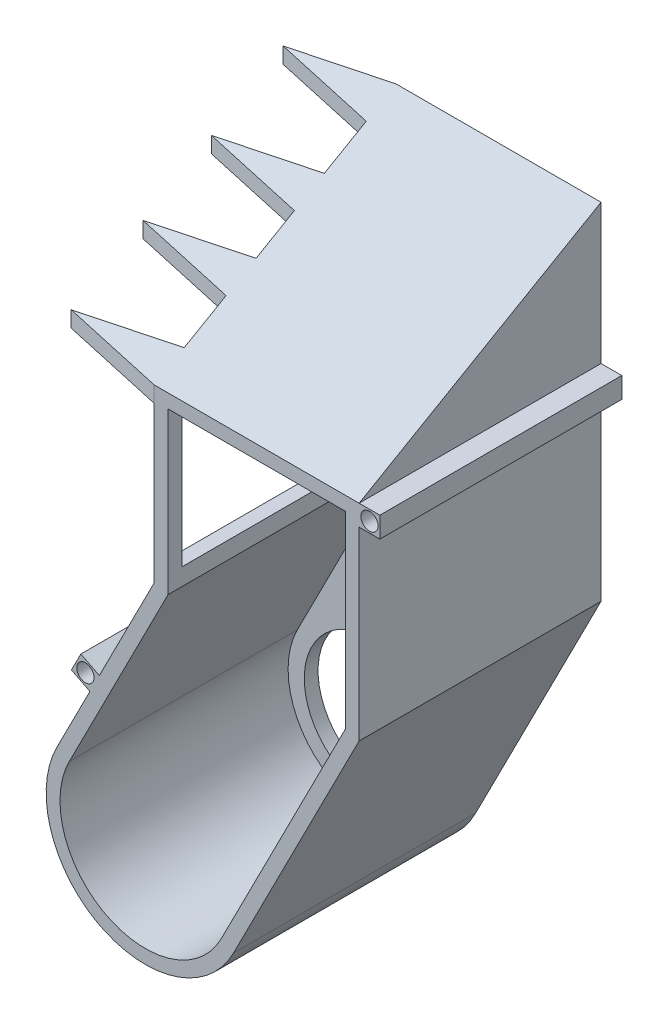
SolidWorks part; units mm, degrees
ref_plane "Front Plane" through (0, 0, 0) normal (0, 0, 1) x (1, 0, 0)
ref_plane "Top Plane" through (0, 0, 0) normal (0, 1, 0) x (1, 0, 0)
ref_plane "Right Plane" through (0, 0, 0) normal (1, 0, 0) x (0, 0, -1)
sketch "Sketch1" plane through (0, 0, 0) normal (0, 0, 1) x (1, 0, 0)
  line L0 (0, 0) -> (0, 26.0789) construction
  line L1 (-32.644, 168.714) -> (42.6346, 168.714)
  line L2 (42.6346, 168.714) -> (42.6346, 41.714)
  line L3 (42.6346, 41.714) -> (-3.4908, -48.8123)
  line L4 (-32.644, 168.714) -> (-32.644, 54.414)
  line L5 (-32.644, 54.414) -> (-68.3912, -15.7439)
  circle A0 centre (-23.0776, 43.8589) radius 3.175
  circle A1 centre (22.1344, 43.8589) radius 3.175
  circle A2 centre (-35.941, -32.2781) radius 25.4
  arc A3 (-68.3912, -15.7439) -> (-3.4908, -48.8123) centre (-35.941, -32.2781) ccw
  dimension "D1" = 50.8
  dimension "D2" = 45.212
  dimension "D3" = 6.35
  dimension "D4" = 6.35
  dimension "D11" = 101.6
  dimension "D5" = 77.216
  dimension "D6" = 95.758
  dimension "D7" = 35.941
  dimension "D8" = 17.78
  dimension "D9" = 153
  dimension "D10" = 127
  dimension "D12" = 78.74
  dimension "D13" = 114.3
  dimension "D14" = 19.05
extrude "Boss-Extrude1" add sketch "Sketch1" along normal blind 88.9
sketch "Sketch2" plane through (-32.644, 0, 0) normal (-1, 0, 0) x (0, 0, 1)
  line L0 (0, 168.714) -> (88.9, 117.3875)
  line L1 (88.9, 168.714) -> (88.9, 54.414) construction
  line L2 (88.9, 117.3875) -> (88.9, 168.714)
  line L3 (88.9, 168.714) -> (0, 168.714)
  dimension "D1" = 30
extrude "Cut-Extrude1" cut sketch "Sketch2" against normal through all
sketch "Sketch3" plane through (0, 0, 88.9) normal (0, 0, 1) x (1, 0, 0)
  line L10 (37.5546, 112.3075) -> (-27.564, 112.3075)
  line L11 (-27.564, 112.3075) -> (-27.564, 53.1944)
  line L12 (-27.564, 53.1944) -> (-63.8649, -18.0502)
  line L13 (-8.0171, -46.506) -> (37.5546, 42.9336)
  line L14 (37.5546, 42.9336) -> (37.5546, 112.3075)
  line L15 (37.5546, 112.3075) -> (-27.564, 112.3075)
  line L16 (-27.564, 112.3075) -> (-27.564, 53.1944)
  line L17 (-27.564, 53.1944) -> (-63.8649, -18.0502)
  line L18 (-8.0171, -46.506) -> (37.5546, 42.9336)
  line L19 (37.5546, 42.9336) -> (37.5546, 112.3075)
  arc A2 (-63.8649, -18.0502) -> (-8.0171, -46.506) centre (-35.941, -32.2781) ccw
  arc A3 (-63.8649, -18.0502) -> (-8.0171, -46.506) centre (-35.941, -32.2781) ccw
  dimension "D1" = 5.08
extrude "Cut-Extrude2" cut sketch "Sketch3" against normal blind 83.82
sketch "Sketch4" plane through (-32.644, 0, 0) normal (-1, 0, 0) x (0, 0, 1)
  line L8 (83.82, 59.494) -> (83.82, 114.4546)
  line L9 (83.82, 114.4546) -> (5.08, 159.9151)
  line L10 (5.08, 159.9151) -> (5.08, 59.494)
  line L11 (5.08, 59.494) -> (83.82, 59.494)
  line L12 (83.82, 59.494) -> (83.82, 114.4546)
  line L13 (83.82, 114.4546) -> (5.08, 159.9151)
  line L14 (5.08, 159.9151) -> (5.08, 59.494)
  line L15 (5.08, 59.494) -> (83.82, 59.494)
  dimension "D1" = 5.08
extrude "Cut-Extrude3" cut sketch "Sketch4" along direction (1, 0, 0) on the side against the normal up to surface (70.1986 mm away) up to face at (37.5546, 77.6205, 46.99)
sketch "Sketch5" plane through (0, 126.5355, 73.0553) normal (0, 0.866, 0.5) x (1, 0, 0)
  line L0 (-32.644, 84.357) -> (-68.6566, 78.007)
  line L1 (-68.6566, 78.007) -> (-32.644, 71.657)
  line L2 (-32.644, 71.657) -> (-32.644, 84.357)
  line L3 (-32.644, 84.357) -> (-32.644, -18.2959) construction
  line L4 (-32.644, 53.877) -> (-68.6566, 47.527)
  line L5 (-68.6566, 47.527) -> (-32.644, 41.177)
  line L6 (-32.644, 41.177) -> (-32.644, 53.877)
  line L7 (-32.644, 24.8841) -> (-68.6566, 18.5341)
  line L8 (-68.6566, 18.5341) -> (-32.644, 12.1841)
  line L9 (-32.644, -49.7827) -> (-32.644, 27.207) construction
  line L10 (-32.644, 12.1841) -> (-32.644, 24.8841)
  line L11 (-32.644, -5.5959) -> (-68.6566, -11.9459)
  line L12 (-68.6566, -11.9459) -> (-32.644, -18.2959)
  line L13 (-32.644, -18.2959) -> (-32.644, -5.5959)
  dimension "D1" = 12.7
  dimension "D2" = 20
  dimension "D3" = 17.78
  dimension "D4" = 17.78
  dimension "D5" = 20
  dimension "D6" = 12.7
  dimension "D7" = 20
  dimension "D8" = 20
extrude "Boss-Extrude2" add sketch "Sketch5" along direction (0, 1, 0) on the side against the normal up to surface (5.08 mm away) up to face at (2.4553, 137.1849, 44.45)
sketch "Sketch6" plane through (0, 0, 88.9) normal (0, 0, 1) x (1, 0, 0)
  line L0 (42.6346, 117.3875) -> (50.2546, 117.3875)
  line L1 (50.2546, 117.3875) -> (50.2546, 109.7675)
  line L2 (50.2546, 109.7675) -> (42.6346, 109.7675)
  line L3 (42.6346, 41.714) -> (42.6346, 117.3875) construction
  line L4 (42.6346, 109.7675) -> (42.6346, 117.3875)
  line L5 (-56.2833, 8.0192) -> (-52.8239, 14.8087)
  line L6 (-32.644, 54.414) -> (-68.3912, -15.7439) construction
  line L7 (-52.8239, 14.8087) -> (-59.6133, 18.2681)
  line L8 (-59.6133, 18.2681) -> (-63.0727, 11.4787)
  line L9 (-63.0727, 11.4787) -> (-56.2833, 8.0192)
  circle A0 centre (46.4446, 113.5775) radius 3.175
  circle A1 centre (-57.9483, 13.1437) radius 3.175
  point P19 (0, 0)
  point P22 (-59.6492, 17.2439)
  dimension "D3" = 6.35
  dimension "D4" = 6.35
  dimension "D1" = 7.62
  dimension "D2" = 44.45
  dimension "D5" = 3.81
  dimension "D6" = 3.81
  dimension "D7" = 3.81
  dimension "D8" = 3.81
extrude "Boss-Extrude3" add sketch "Sketch6" against normal up to surface (88.9 mm away) up to face at (-14.4398, 71.3425, 0)
